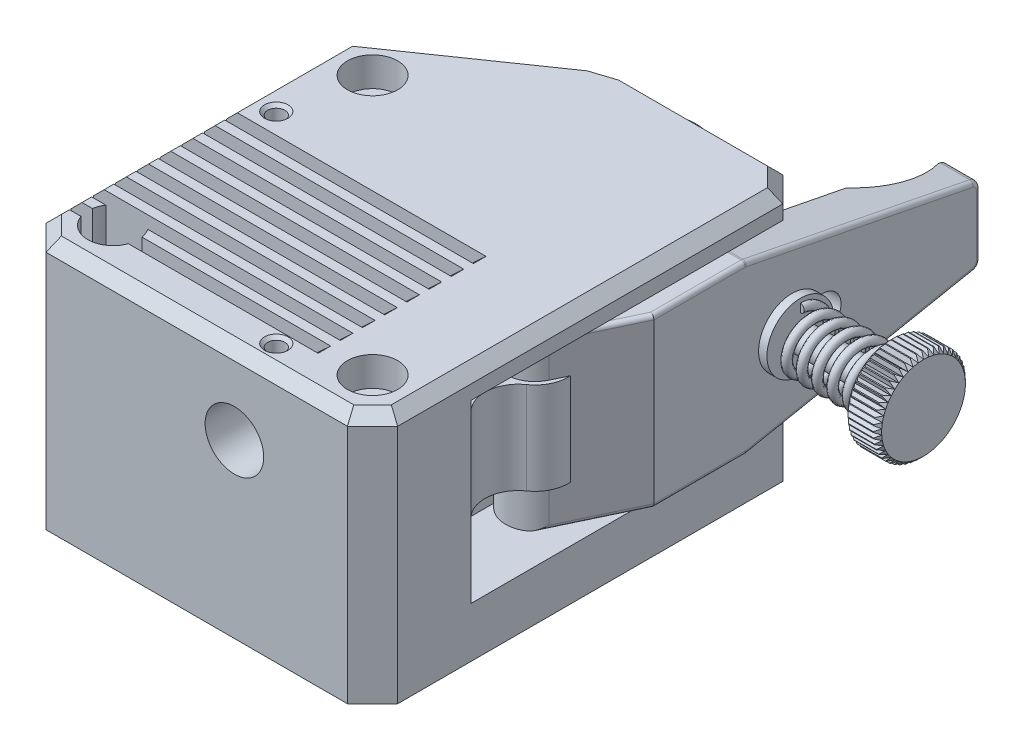
SolidWorks part; units mm, degrees
note: The reader was unsure of these and kept them because the rebuilt part matched: shared geometry of "Skizze3<2>", "Skizze11<2>".
ref_plane "Ebene vorne" through (0, 0, 0) normal (0, 0, 1) x (1, 0, 0)
ref_plane "Ebene oben" through (0, 0, 0) normal (0, 1, 0) x (1, 0, 0)
ref_plane "Ebene rechts" through (0, 0, 0) normal (1, 0, 0) x (0, 0, -1)
sketch "Skizze1" plane through (0, 0, 0) normal (0, 1, 0) x (1, 0, 0)
  line L0 (0, 3) -> (3, 0)
  line L1 (3, 0) -> (39, 0)
  line L2 (39, 0) -> (42, 3)
  line L3 (42, 3) -> (42, 49)
  line L4 (42, 49) -> (39, 52)
  line L5 (39, 52) -> (20.5, 52)
  line L6 (20.5, 52) -> (17.2643, 50.956)
  line L7 (17.2643, 50.956) -> (0, 39)
  line L8 (0, 39) -> (0, 3)
  point P2 (0, 47.9396)
  point P11 (24.1442, 52)
  point P12 (17.044, 51.2361)
  point P13 (17.3483, 51.1347)
  point P14 (15.9241, 51.0499)
  point P15 (16.0118, 50.7661)
  dimension "D1" = 42
  dimension "D2" = 52
  dimension "D3" = 3
  dimension "D4" = 3
  dimension "D5" = 135
  dimension "D6" = 3
  dimension "D7" = 18.5
  dimension "D8" = 36
  dimension "D9" = 3.4
  dimension "D10" = 21
extrude "Aufsatz-Linear austragen1" add sketch "Skizze1" along normal mid plane 30
sketch "Skizze2" plane through (0, 15, 0) normal (0, 1, 0) x (1, 0, 0)
  line L0 (21, 0) -> (21, 52) construction
  line L1 (3, 0) -> (39, 0) construction
  line L2 (39, 52) -> (20.5, 52) construction
  line L5 (21, 21) -> (42, 21) construction
  line L6 (42, 3) -> (42, 49) construction
  line L7 (40.5, 1.5) -> (36.5, 5.5) construction
  line L8 (39, 0) -> (42, 3) construction
  circle A0 centre (36.5, 5.5) radius 1.6
  circle A1 centre (5.5, 5.5) radius 1.6
  circle A2 centre (5.5, 36.5) radius 1.6
  circle A4 centre (36.5, 36.5) radius 1.6 [skipped]
  point P16 (8.0911, 36.7714)
  point P17 (5.241, 5.5)
  point P18 (11.5538, 35.9031)
  point P26 (10.1028, 32.5802)
  dimension "D3" = 3.2
  dimension "D7" = 31
  dimension "D1" = 31
  dimension "D2" = 31
  dimension "D4" = 2
  dimension "D5" = 2
extrude "Schnitt-Linear austragen1" cut sketch "Skizze2" against normal through all and the other way through all
chamfer "Fase1" distance 1.3 angle 45 9 edges at (8.6321, 15, -44.978) (18.8821, 15, -51.478) (29.75, 15, -52) (40.5, 15, -50.5) (42, 15, -26) (40.5, 15, -1.5) (21, 15, 0) (1.5, 15, -1.5) (0, 15, -21)
sketch "Skizze3" plane through (0, 15, 0) normal (0, 1, 0) x (1, 0, 0)
  circle A0 centre (5.5, 5.5) radius 3
  circle A1 centre (36.5, 5.5) radius 3
  circle A2 centre (36.5, 36.5) radius 3 [skipped]
  circle A3 centre (5.5, 36.5) radius 3
  dimension "D1" = 6
  dimension "D2" = 2
  dimension "D3" = 2
extrude "Schnitt-Linear austragen2" cut sketch "Skizze3" against normal blind 3.5
extrude "Schnitt-Linear austragen3" cut sketch "Skizze3<2>" against normal blind 11 contours A0
sketch "Skizze3<2>" plane through (0, 15, 0) normal (0, 1, 0) x (1, 0, 0) same geometry as "Skizze3"
sketch "Skizze4" plane through (0, 0, 0) normal (0, 0, 1) x (1, 0, 0)
  line L0 (0, 15) -> (31, 15)
  line L1 (3.5385, 15) -> (38.4615, 15) construction
  line L2 (0, 13.7) -> (0, -15) construction
  line L3 (0, 4) -> (0, 15)
  line L4 (0, 4) -> (13.5373, 4) construction
  arc A2 (31, 15) -> (15.1508, 5.9444) centre (6.3128, 39.8102) cw
  arc A3 (15.1508, 5.9444) -> (0, 4) centre (0, 64) cw
  point P5 (14.7199, 13.0631)
  point P11 (15.2895, 13.368)
  point P12 (30.8184, 24.1693)
  point P13 (13.5373, 14)
  dimension "D1" = 35
  dimension "D2" = 60
  dimension "D3" = 11
  dimension "D4" = 31
extrude "Schnitt-Linear austragen4" cut sketch "Skizze4" against normal blind 1.5 from offset 4.5 offset against normal yes
pattern_linear "Lineares Muster1" count 8 spacing 2.65 along (0, 0, -1) of "Schnitt-Linear austragen4"
sketch "Skizze5" plane through (0, 15, 0) normal (0, 1, 0) x (1, 0, 0)
  line L0 (15.5, 27) -> (15.5, 4.116) construction
  line L1 (3.5, 27) -> (27.5, 27) construction
  line L2 (27.5, 27) -> (27.5, 3) construction
  line L3 (0, 16.6) -> (0, 15.1) construction
  line L4 (39, 0) -> (3, 0) construction
  line L5 (27.5, 3) -> (3.5, 3) construction
  line L6 (3.5, 3) -> (3.5, 27) construction
  line L7 (3.5, 15) -> (27.5, 15) construction
  circle A0 centre (3.5, 27) radius 1
  circle A1 centre (27.5, 3) radius 1
  point P11 (28, 2.7388)
  point P14 (4, 26.7388)
  dimension "D6" = 2
  dimension "D1" = 24
  dimension "D2" = 24
  dimension "D3" = 15.5
  dimension "D4" = 3
  dimension "D5" = 12
extrude "Schnitt-Linear austragen5" cut sketch "Skizze5" against normal blind 2
hole_wizard "M2.5 Gewindebohrung1" positions "3D-Skizze1" profile "Skizze7" tap size "M2.5" standard "DIN"
sketch3d "3D-Skizze1"
  line L0 (3.5, 13, -27) -> (3.5, 15, -27) construction
  line L1 (27.5, 13, -3) -> (27.5, 15, -3) construction
  point P0 (3.5, 15, -27)
  point P4 (27.5, 15, -3)
sketch "Skizze7" plane through (3.5, 15, -27) normal (1, 0, 0) x (0, 0, 1)
  line L0 (0, 0) -> (0, 5.6159)
  line L1 (0, 5.6159) -> (1.025, 5)
  line L2 (1.025, 5) -> (1.025, 0.375)
  line L3 (1.025, 0.375) -> (1.4, 0)
  line L5 (1.4, 0) -> (0, 0)
  line L6 (-1.025, 0.375) -> (-1.4, 0) construction
  line L10 (0, 5.6159) -> (-1.025, 5) construction
  line L11 (0, -6.35) -> (0, 107.95) construction
  dimension "Bohrerdurchmesser" = 2.05
  dimension "Bohrungstiefe" = 5
  dimension "Senkdurchmesser (Oben)" = 2.8
  dimension "Senkwinkel (Oben)" = 90
  dimension "Spitzenwinkel" = 118
cosmetic thread "Bohrungsgewinde3" parameters "D1"=5, "D2"=2.5
cosmetic thread "Bohrungsgewinde4" parameters "D1"=5, "D2"=2.5
sketch "Skizze8" plane through (0, -15, 0) normal (0, -1, 0) x (1, 0, 0)
  line L0 (34, -52) -> (26.5858, -44.5858)
  line L1 (39, -52) -> (20.5, -52) construction
  line L2 (25.1716, -44) -> (7.2199, -44)
  line L3 (17.2643, -50.956) -> (0, -39) construction
  line L4 (7.2199, -44) -> (18.7718, -52)
  line L5 (18.7718, -52) -> (34, -52)
  line L6 (0, -39) -> (0, -3) construction
  arc A0 (26.5858, -44.5858) -> (25.1716, -44) centre (25.1716, -46) ccw
  point P4 (16.8926, -52)
  point P10 (34, -52)
  point P11 (25.8199, -44)
  point P16 (26, -44)
  dimension "D4" = 2
  dimension "D1" = 8
  dimension "D2" = 5
  dimension "D3" = 26
extrude "Schnitt-Linear austragen6" cut sketch "Skizze8" against normal blind 10
sketch "Skizze9" plane through (0, -15, 0) normal (0, -1, 0) x (1, 0, 0)
  line L0 (5.5, -36.5) -> (5.5, -5.5) construction
  line L1 (5.5, -21) -> (21, -21) construction
  line L2 (21, -21) -> (21, -32.1) construction
  circle A0 centre (21, -21) radius 11.1
  circle A1 centre (36.5, -5.5) radius 1.6 construction
  circle A2 centre (5.5, -5.5) radius 1.6 construction
  dimension "D1" = 22.2
extrude "Schnitt-Linear austragen7" cut sketch "Skizze9" against normal blind 10 contours A0
sketch "Skizze10" plane through (0, -15, 0) normal (0, -1, 0) x (1, 0, 0)
  line L0 (37.8, -52) -> (37.8, -44)
  line L1 (39, -52) -> (34, -52) construction
  line L2 (37.8, -44) -> (32, -44)
  line L3 (32, -44) -> (32, -29)
  line L4 (32, -29) -> (36.406, -29)
  line L5 (38.1458, -15.6042) -> (42, -11.75)
  line L6 (42, -3) -> (42, -49) construction
  line L7 (42, -11.75) -> (42, -52)
  line L8 (42, -52) -> (37.8, -52)
  arc A0 (36.406, -29) -> (38.6901, -21.7163) centre (36.406, -25) ccw
  arc A1 (38.6901, -21.7163) -> (38.1458, -15.6042) centre (40.9743, -18.4326) cw
  point P14 (38.7217, -21.7385)
  dimension "D4" = 4
  dimension "D8" = 4
  dimension "D1" = 8
  dimension "D2" = 4.2
  dimension "D3" = 8.75
  dimension "D5" = 10
  dimension "D6" = 22
  dimension "D7" = 5.594
  dimension "D9" = 45
extrude "Schnitt-Linear austragen8" cut sketch "Skizze10" against normal offset from surface (21 mm away) 3 from offset 6 up to face at (3.5, 15, -25.6) offset against normal yes
sketch "Skizze11" plane through (0, -15, 0) normal (0, -1, 0) x (1, 0, 0)
  line L0 (42, -11.75) -> (33, -20.75)
  line L1 (42, -3) -> (42, -49) construction
  line L2 (33, -20.75) -> (33, -39.8255)
  line L3 (33, -39.8255) -> (42, -39.8255)
  line L4 (42, -39.8255) -> (42, -11.75)
  line L5 (42, -11.75) -> (38.1458, -15.6042) construction
  dimension "D1" = 9
extrude "Schnitt-Linear austragen9" cut sketch "Skizze11" against normal blind 5 from surface at -6 starting at face at (37.7089, -9, -34.9036)
extrude "Schnitt-Linear austragen10" cut sketch "Skizze11<2>" along normal blind 5 from surface at -27 starting at face at (37.7089, 12, -34.9036)
sketch "Skizze11<2>" plane through (0, -15, 0) normal (0, -1, 0) x (1, 0, 0) same geometry as "Skizze11"
sketch "Skizze12" plane through (0, 0, 0) normal (0, 1, 0) x (1, 0, 0)
  line L0 (43.6, 71) -> (43.6, 32)
  line L1 (43.6, 32) -> (39.5683, 23.5001)
  line L2 (33.0613, 26.031) -> (38.6, 44)
  line L3 (38.6, 44) -> (38.6, 71)
  line L4 (38.6, 71) -> (43.6, 71)
  line L5 (37.8, 44) -> (37.8, 52) construction
  line L6 (32, 44) -> (37.8, 44) construction
  line L7 (20.5, 52) -> (39, 52) construction
  arc A0 (39.5683, 23.5001) -> (33.0613, 26.031) centre (36.406, 25) cw
  arc A1 (38.6901, 21.7163) -> (36.406, 29) centre (36.406, 25) ccw construction
  point P9 (36.9333, 24.3101)
  point P13 (0, 0)
  point P14 (43.6, 36.3583)
  point P15 (41.4848, 23.705)
  point P16 (0, 0)
  point P17 (38.6, 44.2546)
  point P20 (0, 0)
  dimension "D4" = 3.5
  dimension "D1" = 5
  dimension "D2" = 0.8
  dimension "D3" = 7
  dimension "D5" = 19
extrude "Aufsatz-Linear austragen2" add sketch "Skizze12" along normal mid plane 20 from offset 1.5
sketch "Skizze14" plane through (43.6, 0, 0) normal (1, 0, 0) x (0, 0, -1)
  line L0 (71, 6) -> (43, 11.5)
  line L1 (71, 11.5) -> (71, -8.5) construction
  line L2 (32, 11.5) -> (71, 11.5) construction
  line L3 (43, 11.5) -> (71, 11.5)
  line L4 (71, 11.5) -> (71, 6)
  line L5 (71, 1.5) -> (32, 1.5) construction
  line L6 (32, 11.5) -> (32, -8.5) construction
  line L7 (71, -8.5) -> (71, -3)
  line L8 (43, -8.5) -> (71, -8.5)
  line L9 (71, -3) -> (43, -8.5)
  dimension "D1" = 9
  dimension "D2" = 28
extrude "Schnitt-Linear austragen11" cut sketch "Skizze14" against normal up to next contours L0 L3 L4
fillet "Verrundung1" radius 1 4 edges at (40.9459, -8.5, -43) (40.9459, 11.5, -43) (41.1, -3, -71) (41.1, 6, -71)
sketch "Skizze15" plane through (43.6, 0, 0) normal (1, 0, 0) x (0, 0, -1)
  line L0 (52.2, 1.5) -> (48.8, 1.5) construction
  line L1 (52.2, -0.65) -> (48.8, -0.65)
  line L2 (52.2, 3.65) -> (48.8, 3.65)
  line L3 (32, 11.5) -> (42.9027, 11.5) construction
  line L4 (32, -8.5) -> (42.9027, -8.5) construction
  line L5 (52, -9) -> (52, -15) construction
  arc A0 (52.2, -0.65) -> (52.2, 3.65) centre (52.2, 1.5) ccw
  arc A1 (48.8, 3.65) -> (48.8, -0.65) centre (48.8, 1.5) ccw
  point P2 (50.5, 1.5)
  point P11 (52.4363, 3.65)
  dimension "D1" = 2.15
  dimension "D2" = 3.4
  dimension "D3" = 0.2
extrude "Schnitt-Linear austragen12" cut sketch "Skizze15" against normal up to next
sketch "Skizze16" plane through (0, 0, 0) normal (0, 1, 0) x (1, 0, 0)
  line L0 (39.6, 71) -> (38.6, 71)
  line L1 (38.6, 71) -> (38.6, 60)
  line L2 (38.6, 70.1927) -> (38.6, 44) construction
  line L3 (38.6, 71) -> (43.6, 71) construction
  line L4 (39.6, 71) -> (39.6, 70)
  line L5 (43.6, 43.0955) -> (43.6, 70.1927) construction
  arc A1 (38.6, 60) -> (39.6, 70) centre (29.7901, 65.931) ccw
  point P5 (0, 0)
  dimension "D2" = 10.6203
  dimension "D1" = 4
  dimension "D3" = 11
  dimension "D4" = 1
extrude "Schnitt-Linear austragen13" cut sketch "Skizze16" against normal mid plane 30
ref_plane "Ebene1" through (0, 1.5, 0) normal (0, -1, 0) x (-1, 0, 0)
sketch "Skizze18" plane through (0, 1.5, 0) normal (0, 1, 0) x (1, 0, 0)
  line L0 (37.8, 48.5) -> (54.8767, 48.5) construction
  line L1 (37.8, 44) -> (37.8, 52) construction
  line L2 (20.5, 52) -> (39, 52) construction
  line L4 (55.3, 50) -> (55.3, 54)
  line L5 (55.3, 54) -> (59.3, 54)
  line L6 (59.3, 54) -> (59.3, 48.5)
  line L7 (59.3, 48.5) -> (37.8, 48.5)
  line L8 (37.8, 48.5) -> (37.8, 50)
  line L9 (43.6, 43.0955) -> (43.6, 70.1927) construction
  line L10 (55.3, 50) -> (44.6, 50)
  line L11 (44.6, 50) -> (44.6, 52.5)
  line L12 (44.6, 52.5) -> (43.6, 52.5)
  line L13 (43.6, 52.2) -> (43.6, 54.35) construction
  line L14 (43.6, 52.5) -> (43.6, 50)
  line L15 (43.6, 52.2) -> (43.6, 48.8) construction
  line L16 (43.6, 50) -> (37.8, 50)
  dimension "D1" = 3.5
  dimension "D2" = 1.5
  dimension "D3" = 4
  dimension "D4" = 5.5
  dimension "D5" = 11.7
  dimension "D6" = 1
  dimension "D7" = 4
revolve "Rotation1" add sketch "Skizze18" angle 360 about L0
sketch "Skizze20" plane through (44.6, 0, 0) normal (1, 0, 0) x (0, 0, -1)
  circle A0 centre (48.5, 1.5) radius 3
  dimension "D1" = 6
curve "Spirale/Helix1" pitch 1.8333 height 11 turns 6
ref_plane "Ebene2" through (44.6, 4.5, -48.5) normal (0.0968, 0, -0.9953) x (-0.9953, 0, -0.0968)
sketch "Skizze21" plane through (44.6, 4.5, -48.5) normal (0.0968, 0, -0.9953) x (-0.9953, 0, -0.0968)
  circle A0 centre (0, 0) radius 0.5
  point P2 (0, 0)
  dimension "D1" = 1
sweep "Austragung1" add profiles "Skizze21" path "Spirale/Helix1"
chamfer "Fase2" distance 0.5 angle 45 2 edges at (59.3, 1.5, -43) (55.3, 1.5, -43)
sketch "Skizze22" plane through (59.3, 0, 0) normal (1, 0, 0) x (0, 0, -1)
  line L0 (48.5, 7) -> (48.5, 1.5) construction
  line L1 (48.2, 7) -> (48.8, 7)
  line L2 (48.8, 7) -> (48.5, 6.5)
  line L3 (48.5, 6.5) -> (48.2, 7)
  circle A0 centre (48.5, 1.5) radius 5.5 construction
  point P7 (0, 0)
  dimension "D1" = 0.6
  dimension "D2" = 0.5
extrude "Schnitt-Linear austragen14" cut sketch "Skizze22" against normal up to next
pattern_circular "Kreismuster1" count 50 over 360 about axis through (0, 1.5, -48.5) along (1, 0, 0) of "Schnitt-Linear austragen14"
sketch "Skizze23" plane through (0, 0, 0) normal (0, 0, 1) x (1, 0, 0)
  line L1 (42, 13.7) -> (42, -15) construction
  line L2 (3.5385, 15) -> (38.4615, 15) construction
  circle A0 centre (25.5, 5.5) radius 3.5
  dimension "D1" = 7
  dimension "D2" = 9.5
  dimension "D3" = 16.5
extrude "Schnitt-Linear austragen15" cut sketch "Skizze23" against normal blind 30
fillet "Verrundung2" radius 0.5 7 edges at (41.5842, 11.5, -27.75) (43.6, -8.5, -37.4514) (43.6, -5.8199, -56.6441) (43.6, 1.5, -71) (43.6, 8.8199, -56.6441) (41.5842, -8.5, -27.75) (43.6, 11.5, -37.4514)
sketch "Skizze24" plane through (0, 0, 0) normal (0, 0, 1) x (1, 0, 0)
  point P0 (25.5, 5.5)
  point P1 (0, 0)
ref_plane "Ebene3" through (0, 5.5, 0) normal (0, 1, 0) x (1, 0, 0)
sketch "Skizze25" plane through (0, 5.5, 0) normal (0, 1, 0) x (1, 0, 0)
  line L0 (25.5, 0) -> (25.5, 52) construction
  line L1 (20.5, 52) -> (39, 52) construction
  line L2 (20.3, 52) -> (23.25, 52)
  line L3 (20.3, 52) -> (20.3, 53)
  line L4 (20.3, 53) -> (22.25, 53)
  line L5 (22.25, 53) -> (22.25, 54)
  line L6 (22.25, 54) -> (20.3, 54)
  line L7 (20.3, 54) -> (20.3, 55.1)
  line L8 (20.3, 55.1) -> (23.25, 55.1)
  line L9 (23.25, 55.1) -> (23.25, 52)
  point P11 (24.0278, 52.0965)
  point P13 (21.775, 55.1)
  dimension "D1" = 1
  dimension "D2" = 10.4
  dimension "D3" = 1
  dimension "D4" = 1.1
  dimension "D5" = 2.25
  dimension "D6" = 1
revolve "Rotation2" add sketch "Skizze25" angle 360 about L0
